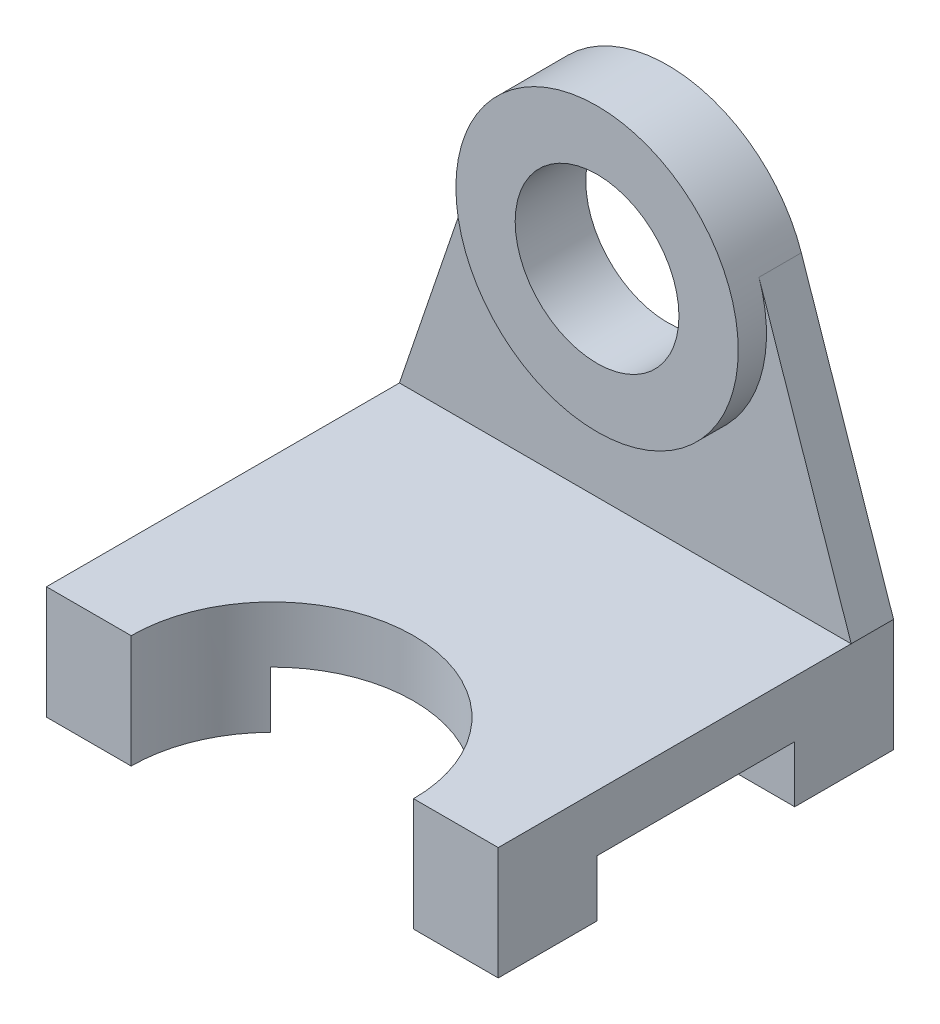
SolidWorks part; units mm, degrees
ref_plane "前视基准面" through (0, 0, 0) normal (0, 0, 1) x (1, 0, 0)
ref_plane "上视基准面" through (0, 0, 0) normal (0, 1, 0) x (1, 0, 0)
ref_plane "右视基准面" through (0, 0, 0) normal (1, 0, 0) x (0, 0, -1)
other "Configuration Table"
sketch "草图1" plane through (0, 0, 0) normal (0, 1, 0) x (1, 0, 0)
  line L1 (0, 0) -> (160, 0)
  line L2 (0, 0) -> (0, -140)
  line L3 (0, -140) -> (160, -140)
  line L4 (160, 0) -> (160, -140)
  arc A0 (130, -140) -> (30, -140) centre (80, -140) ccw
  dimension "D3" = 100
  dimension "D1" = 160
  dimension "D2" = 140
extrude "凸台-拉伸1" add sketch "草图1" along normal blind 40 contours A0 L3 L4 L1 L2 region at (80, 0, 59.6305)
sketch "草图4" plane through (0, 0, 0) normal (-1, 0, 0) x (0, 0, 1)
  line L0 (0, 0) -> (140, 0) construction
  line L1 (0, 0) -> (140, 0)
  line L2 (35, 0) -> (105, 0)
  line L3 (105, 0) -> (105, 20)
  line L4 (105, 20) -> (35, 20)
  line L6 (35, 0) -> (35, 20)
  dimension "D2" = 20
  dimension "D3" = 70
extrude "切除-拉伸1" cut sketch "草图4" against normal through all both and the other way through all contours L6 L1 L3 L4 region at (0, 10, 70)
sketch "草图5" plane through (0, 0, 0) normal (0, 0, -1) x (-1, 0, 0)
  line L1 (-80, 40) -> (-80, 107.9868) construction
  line L3 (0, 40) -> (-160, 40) construction
  line L4 (-160, 40) -> (-127.3403, 136.0903)
  line L5 (0, 40) -> (-32.6597, 136.0903)
  circle A0 centre (-80, 120) radius 29
  circle A1 centre (-80, 120) radius 50
  point P3 (-80, 40)
  line M7 (0, 40) -> (-160, 40)
  dimension "D1" = 58
  dimension "D2" = 100
  dimension "D3" = 120
extrude "凸台-拉伸2" add sketch "草图5" against normal blind 15 contours L1 L5 A1 M7 | L1 A1 L4 M7 region at (121.007, 64.9294, 0) region at (38.993, 64.9294, 0)
extrude "凸台-拉伸3" add sketch "草图5<3>" against normal blind 25 contours A1 L1 A0 | L1 A1 A0 region at (119.4983, 91.7075, 0)
sketch "草图5<3>" plane through (0, 0, 0) normal (0, 0, -1) x (-1, 0, 0) same geometry as "草图5"
